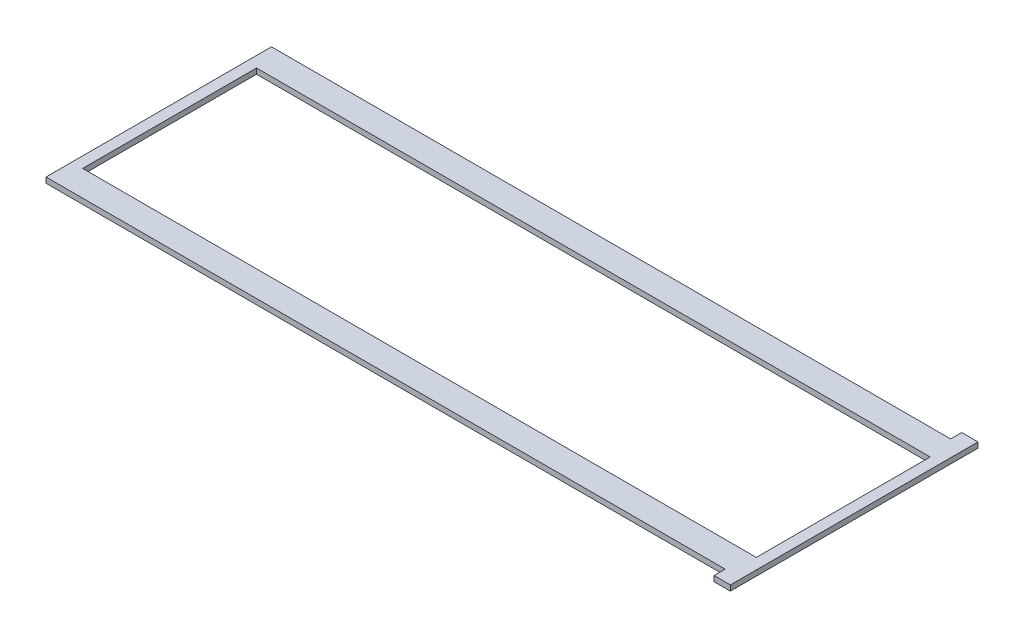
SolidWorks part; units mm, degrees
ref_plane "Front" through (0, 0, 0) normal (0, 0, 1) x (1, 0, 0)
ref_plane "Top" through (0, 0, 0) normal (0, 1, 0) x (1, 0, 0)
ref_plane "Right" through (0, 0, 0) normal (1, 0, 0) x (0, 0, -1)
sketch "Sketch1" plane through (0, 0, 0) normal (0, 1, 0) x (1, 0, 0)
  line L1 (-203.2, -72.3614) -> (203.2, -72.3614)
  line L2 (-203.2, -72.3614) -> (-203.2, 72.3614)
  line L3 (-203.2, 72.3614) -> (203.2, 72.3614)
  line L4 (203.2, -72.3614) -> (203.2, 72.3614)
  line L5 (-203.2, -72.3614) -> (203.2, 72.3614) construction
  line L6 (-203.2, 72.3614) -> (203.2, -72.3614) construction
  line L7 (-203.2, 72.3614) -> (193.675, 72.3614)
  line L8 (-203.2, 72.3614) -> (-203.2, 65.8844)
  line L9 (-203.2, 65.8844) -> (193.675, 65.8844)
  line L10 (193.675, 72.3614) -> (193.675, 65.8844)
  line L11 (-203.2, -72.3614) -> (193.675, -72.3614)
  line L12 (-203.2, -72.3614) -> (-203.2, -65.8844)
  line L13 (-203.2, -65.8844) -> (193.675, -65.8844)
  line L14 (193.675, -72.3614) -> (193.675, -65.8844)
  line L15 (-196.85, -50.8508) -> (196.85, -50.8508)
  line L16 (-196.85, -50.8508) -> (-196.85, 50.8)
  line L17 (-196.85, 50.8) -> (196.85, 50.8)
  line L18 (196.85, -50.8508) -> (196.85, 50.8)
  point P0 (0, 0)
  point P12 (0, 0)
  dimension "D2" = 406.4
  dimension "D3" = 9.525
  dimension "D4" = 6.477
  dimension "D5" = 101.6508
  dimension "D6" = 6.35
  dimension "D7" = 50.8
  dimension "D8" = 6.35
extrude "Boss-Extrude1" add sketch "Sketch1" along normal blind 3.175 contours L14 L1 L4 L3 L10 L9 L2 L13 L18 L15 L16 L17 region at (197.989, 0, 69.1229)
equation "\"D1@Sketch1\"    = 4.98025 - 0.002 + 2 * ( 0.25 + 0.016 + ( 6 / 64 ) )"
